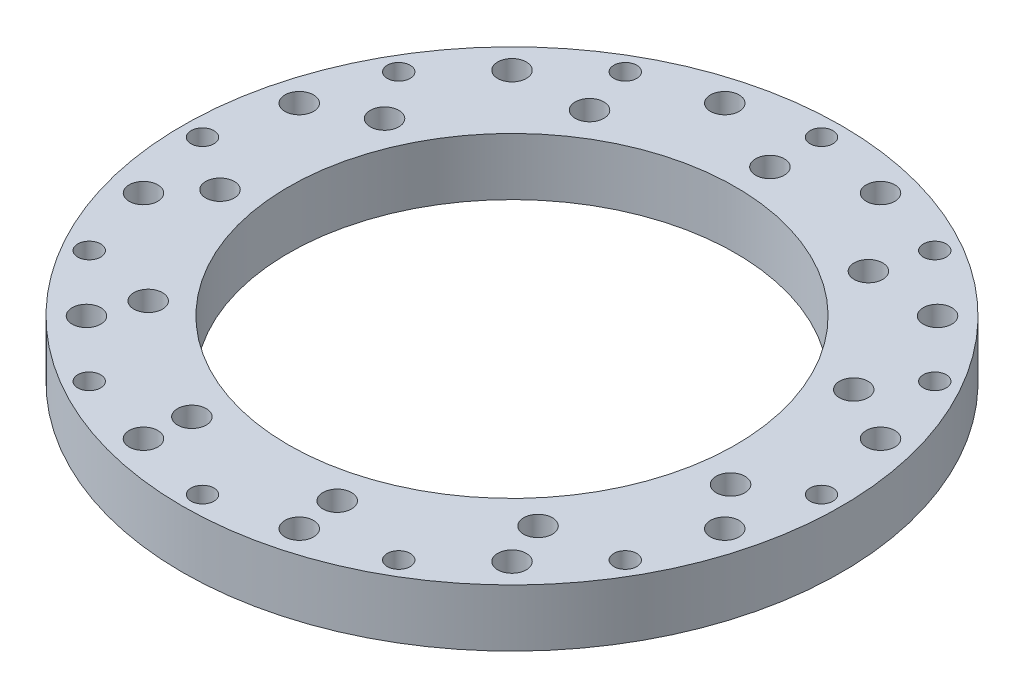
SolidWorks part; units mm, degrees
ref_plane "Front Plane" through (0, 0, 0) normal (0, 0, 1) x (1, 0, 0)
ref_plane "Top Plane" through (0, 0, 0) normal (0, 1, 0) x (1, 0, 0)
ref_plane "Right Plane" through (0, 0, 0) normal (1, 0, 0) x (0, 0, -1)
sketch "Sketch1" plane through (0, 0, 0) normal (0, 1, 0) x (1, 0, 0)
  line L0 (0, 0) -> (0, 52.5) construction
  line L1 (0, 0) -> (13.588, 50.7111) construction
  circle A12 centre (0, 0) radius 39
  circle A13 centre (0, 0) radius 57.5
  circle A14 centre (0, 0) radius 54 construction
  circle A15 centre (0, 54) radius 2
  circle A16 centre (27, 46.7654) radius 2
  circle A17 centre (46.7654, 27) radius 2
  circle A18 centre (54, 0) radius 2
  circle A19 centre (46.7654, -27) radius 2
  circle A20 centre (27, -46.7654) radius 2
  circle A21 centre (0, -54) radius 2
  circle A22 centre (-27, -46.7654) radius 2
  circle A23 centre (-46.7654, -27) radius 2
  circle A24 centre (-54, 0) radius 2
  circle A25 centre (-46.7654, 27) radius 2
  circle A26 centre (-27, 46.7654) radius 2
  circle A27 centre (0, 0) radius 52.5 construction
  circle A34 centre (13.588, 50.7111) radius 2.5
  circle A35 centre (37.1231, 37.1231) radius 2.5
  circle A36 centre (50.7111, 13.588) radius 2.5
  circle A37 centre (50.7111, -13.588) radius 2.5
  circle A38 centre (37.1231, -37.1231) radius 2.5
  circle A39 centre (13.588, -50.7111) radius 2.5
  circle A40 centre (-13.588, -50.7111) radius 2.5
  circle A41 centre (-37.1231, -37.1231) radius 2.5
  circle A42 centre (-50.7111, -13.588) radius 2.5
  circle A43 centre (-50.7111, 13.588) radius 2.5
  circle A44 centre (-37.1231, 37.1231) radius 2.5
  circle A45 centre (-13.588, 50.7111) radius 2.5
  point P21 (0, 0)
  point P28 (0, 0)
  point P56 (0, 0)
  point P60 (0, 0)
  dimension "D1" = 105
  dimension "D2" = 15
  dimension "D4" = 115
  dimension "D5" = 78
  dimension "D6" = 108
  dimension "D7" = 4
  dimension "D3" = 5
  dimension "D8" = 12
extrude "Boss-Extrude1" add sketch "Sketch1" along normal blind 10
sketch "Sketch2" plane through (0, 10, 0) normal (0, 1, 0) x (1, 0, 0)
  circle A0 centre (0, 0) radius 45 construction
  circle A1 centre (0, 45) radius 2.5
  circle A2 centre (24.3288, 37.8564) radius 2.5
  circle A3 centre (40.9334, 18.6937) radius 2.5
  circle A4 centre (44.542, -6.4042) radius 2.5
  circle A5 centre (34.0087, -29.4687) radius 2.5
  circle A6 centre (12.678, -43.1772) radius 2.5
  circle A7 centre (-12.678, -43.1772) radius 2.5
  circle A8 centre (-34.0087, -29.4687) radius 2.5
  circle A9 centre (-44.542, -6.4042) radius 2.5
  circle A10 centre (-40.9334, 18.6937) radius 2.5
  circle A11 centre (-24.3288, 37.8564) radius 2.5
  point P27 (0, 0)
  dimension "D1" = 90
  dimension "D2" = 5
extrude "Cut-Extrude1" cut sketch "Sketch2" against normal blind 10
